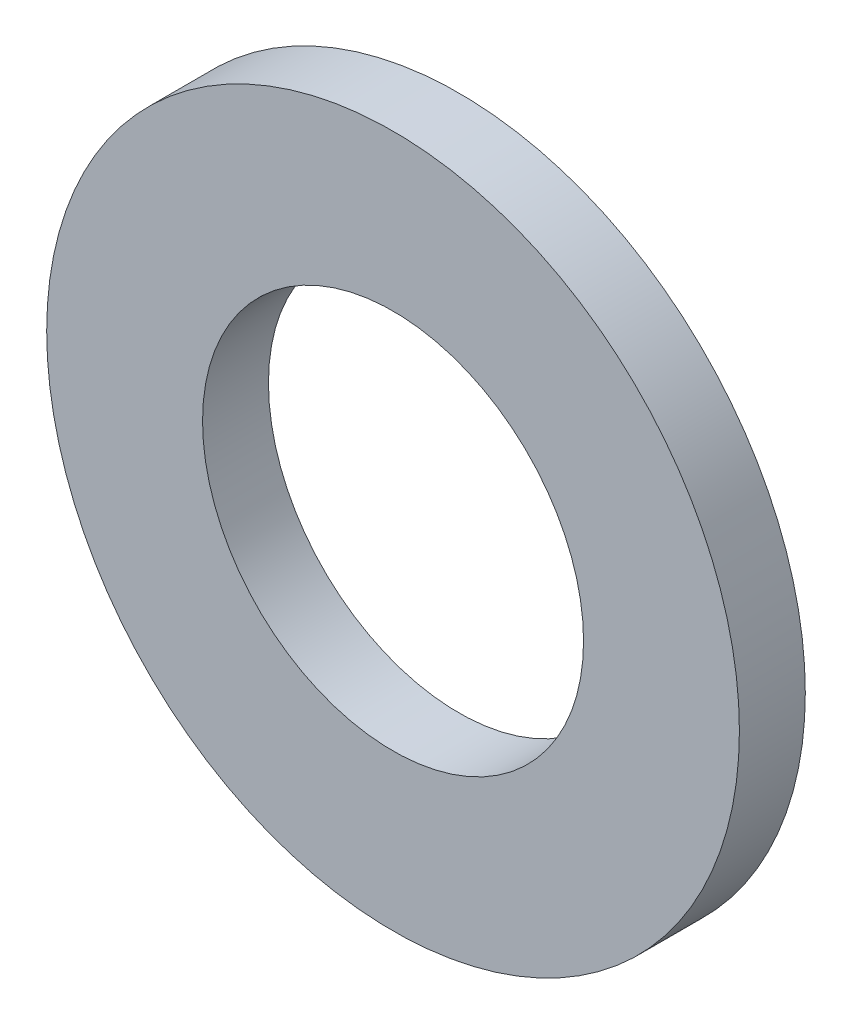
SolidWorks part; units mm, degrees
material "Nylon 101"
ref_plane "Front Plane" through (0, 0, 0) normal (0, 0, 1) x (1, 0, 0)
ref_plane "Top Plane" through (0, 0, 0) normal (0, 1, 0) x (1, 0, 0)
ref_plane "Right Plane" through (0, 0, 0) normal (1, 0, 0) x (0, 0, -1)
sketch "Sketch1" plane through (0, 0, 0) normal (0, 0, 1) x (1, 0, 0)
  circle A0 centre (0, 0) radius 9.525
  circle A1 centre (0, 0) radius 5.2387
  dimension "D1" = 19.05
  dimension "D2" = 10.4775
extrude "Boss-Extrude1" add sketch "Sketch1" along normal mid plane 1.8125
equation "\"D1@Boss-Extrude1\"=0.0625in+0.45mm/2"
